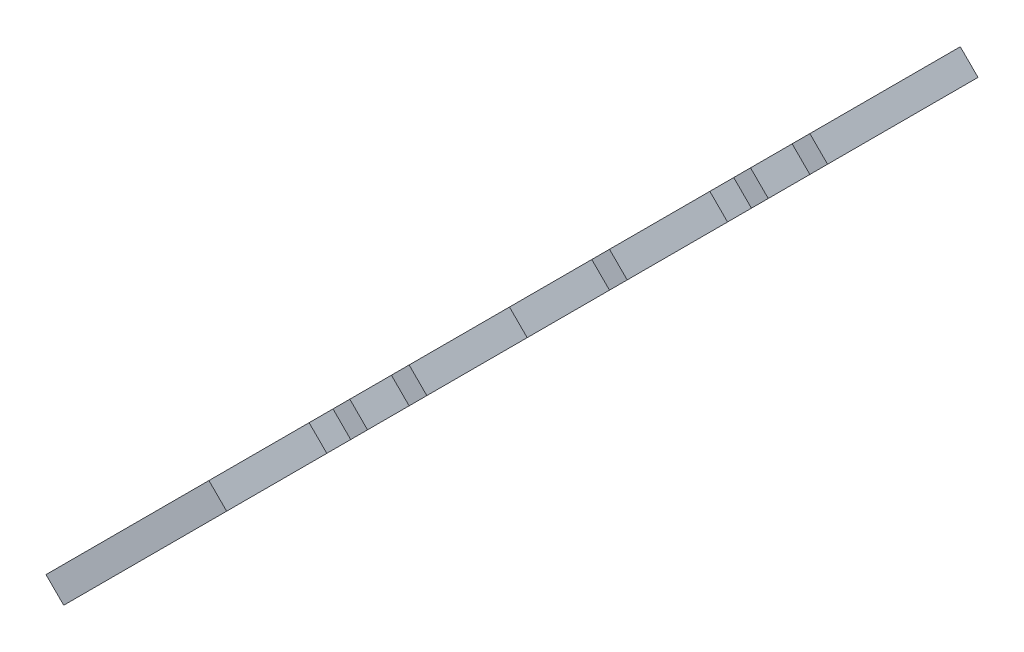
SolidWorks part; units mm, degrees
ref_plane "Front Plane" through (0, 0, 0) normal (0, 0, 1) x (1, 0, 0)
ref_plane "Top Plane" through (0, 0, 0) normal (0, 1, 0) x (1, 0, 0)
ref_plane "Right Plane" through (0, 0, 0) normal (1, 0, 0) x (0, 0, -1)
sketch "Sketch1" plane through (0, 0, 0) normal (0, 0, 1) x (1, 0, 0)
  line L0 (-110.4572, 6.7859) -> (-69.148, 48.095)
  line L1 (-110.4572, 6.7859) -> (-114.9473, 11.276)
  line L2 (-69.148, 48.095) -> (-73.6381, 52.5852)
  line L3 (-114.9473, 11.276) -> (-73.6381, 52.5852)
  line L4 (-74.5361, -29.1352) -> (-70.046, -24.645) construction
extrude "Boss-Extrude1" add sketch "Sketch1" along normal up to surface (190.5 mm away)
sketch "Sketch2" plane through (-63.1116, 63.1116, 0) normal (-0.7071, 0.7071, 0) x (0, 0, 1)
  line L0 (190.5, -14.8867) -> (0, -14.8867) construction
  line L1 (165.1, -21.2367) -> (139.7412, -21.2367)
  line L2 (165.1, -21.2367) -> (165.1, -14.8867)
  line L3 (165.1, -14.8867) -> (139.7412, -14.8867)
  line L4 (139.7412, -21.2367) -> (139.7412, -14.8867)
  line L5 (190.5, -73.3067) -> (0, -73.3067) construction
  line L6 (165.1, -66.9567) -> (139.7412, -66.9567)
  line L7 (165.1, -66.9567) -> (165.1, -73.3067)
  line L8 (165.1, -73.3067) -> (139.7412, -73.3067)
  line L9 (139.7412, -66.9567) -> (139.7412, -73.3067)
  dimension "D1" = 25.3588
extrude "Cut-Extrude1" cut sketch "Sketch2" against normal blind 6.35
pattern_linear "LPattern1" count 3 spacing 50.8 along (0, 0, -1) of "Cut-Extrude1"
sketch "Sketch3" plane through (0, 0, 0) normal (0, 0, -1) x (-1, 0, 0)
  line L0 (94.2927, 22.9503) -> (98.7828, 27.4404)
  line L1 (110.4572, 6.7859) -> (69.148, 48.095) construction
  line L2 (73.6381, 52.5852) -> (114.9473, 11.276) construction
  line L3 (98.7828, 27.4404) -> (89.8026, 36.4207)
  line L4 (89.8026, 36.4207) -> (85.3124, 31.9306)
  line L6 (85.3124, 31.9306) -> (94.2927, 22.9503)
  line L7 (98.7828, 36.4207) -> (83.4753, 21.1131) construction
  line L8 (69.148, 48.095) -> (73.6381, 52.5852) construction
  line L9 (114.9473, 11.276) -> (110.4572, 6.7859) construction
  dimension "D1" = 12.7
  dimension "D2" = 6.35
extrude "Boss-Extrude2" add sketch "Sketch3" along normal blind 6.35
sketch "Sketch5" plane through (-58.6215, 58.6215, 0) normal (0.7071, -0.7071, 0) x (0, 0, -1)
  line L0 (-179.9336, -73.3067) -> (-175.6664, -66.9567) construction
  line L1 (-190.5, -73.3067) -> (-165.1, -73.3067) construction
  line L2 (-179.9336, -66.9567) -> (-179.9336, -73.3067) construction
  line L3 (-175.6664, -73.3067) -> (-179.9336, -66.9567) construction
  line L4 (-175.6664, -66.9567) -> (-175.6664, -73.3067) construction
  line L5 (-78.3336, -73.3067) -> (-74.0664, -66.9567) construction
  line L6 (-88.9412, -73.3067) -> (-63.5, -73.3067) construction
  line L7 (-78.3336, -66.9567) -> (-78.3336, -73.3067) construction
  line L8 (-74.0664, -73.3067) -> (-78.3336, -66.9567) construction
  line L9 (-74.0664, -66.9567) -> (-74.0664, -73.3067) construction
  line L10 (-18.0086, -73.3067) -> (-13.7414, -66.9567) construction
  line L11 (-38.1412, -73.3067) -> (0, -73.3067) construction
  line L12 (-18.0086, -66.9567) -> (-18.0086, -73.3067) construction
  line L13 (-13.7414, -73.3067) -> (-18.0086, -66.9567) construction
  line L14 (-13.7414, -66.9567) -> (-13.7414, -73.3067) construction
  circle A0 centre (-177.8, -70.1317) radius 2.0955
  circle A1 centre (-76.2, -70.1317) radius 2.0955
  circle A2 centre (-15.875, -70.1317) radius 2.0955
  dimension "D1" = 4.191
extrude "Cut-Extrude2" cut sketch "Sketch5" against normal through all
ref_plane "Midplane" through (-31.1811, -31.1811, 0) normal (-0.7071, -0.7071, 0) x (-0.7071, 0.7071, 0)
mirror "Mirror1" about plane through (-31.1811, -31.1811, 0) normal (-0.7071, -0.7071, 0) of "Cut-Extrude2"
sketch "Sketch6" plane through (-63.1116, 63.1116, 0) normal (-0.7071, 0.7071, 0) x (0, 0, 1)
  line L0 (152.4206, -3.6091) -> (152.4206, -40.9822) construction
  line L1 (139.7412, -14.8867) -> (139.7412, -21.2367) construction
  line L2 (165.1, -21.2367) -> (165.1, -14.8867) construction
  line L3 (50.8206, 6.6062) -> (50.8206, -35.0025) construction
  line L4 (38.1412, -14.8867) -> (38.1412, -21.2367) construction
  line L5 (63.5, -21.2367) -> (63.5, -14.8867) construction
  line L7 (38.1412, -21.2367) -> (63.5, -21.2367) construction
  line L11 (139.7412, -21.2367) -> (165.1, -21.2367) construction
  line B0 (52.9542, -21.2367) -> (48.687, -21.2367)
  line B1 (48.687, -33.1747) -> (46.3756, -33.1747)
  line B2 (46.3756, -33.1747) -> (46.3756, -29.9997)
  line B3 (46.3756, -29.9997) -> (48.687, -29.9997)
  line B4 (48.687, -29.9997) -> (48.687, -21.2367)
  line B5 (48.687, -33.1747) -> (48.687, -36.4767)
  line B6 (48.687, -36.4767) -> (52.9542, -36.4767)
  line B7 (52.9542, -33.1747) -> (52.9542, -36.4767)
  line B8 (52.9542, -29.9997) -> (52.9542, -21.2367)
  line B9 (55.2656, -29.9997) -> (52.9542, -29.9997)
  line B10 (55.2656, -33.1747) -> (55.2656, -29.9997)
  line B11 (52.9542, -33.1747) -> (55.2656, -33.1747)
  line B12 (154.5542, -21.2367) -> (150.287, -21.2367)
  line B13 (150.287, -33.1747) -> (147.9756, -33.1747)
  line B14 (147.9756, -33.1747) -> (147.9756, -29.9997)
  line B15 (147.9756, -29.9997) -> (150.287, -29.9997)
  line B16 (150.287, -29.9997) -> (150.287, -21.2367)
  line B17 (150.287, -33.1747) -> (150.287, -36.4767)
  line B18 (150.287, -36.4767) -> (154.5542, -36.4767)
  line B19 (154.5542, -33.1747) -> (154.5542, -36.4767)
  line B20 (154.5542, -29.9997) -> (154.5542, -21.2367)
  line B21 (156.8656, -29.9997) -> (154.5542, -29.9997)
  line B22 (156.8656, -33.1747) -> (156.8656, -29.9997)
  line B23 (154.5542, -33.1747) -> (156.8656, -33.1747)
sketch_block_instance "TSlot-1"
sketch_block "TSlot" parameters "D1"=3.302, "D2"=3.175
sketch_block_instance "TSlot-2"
extrude "Cut-Extrude3" cut sketch "Sketch6" against normal through all
mirror "Mirror2" about plane through (-31.1811, -31.1811, 0) normal (-0.7071, -0.7071, 0) of "Cut-Extrude3"
